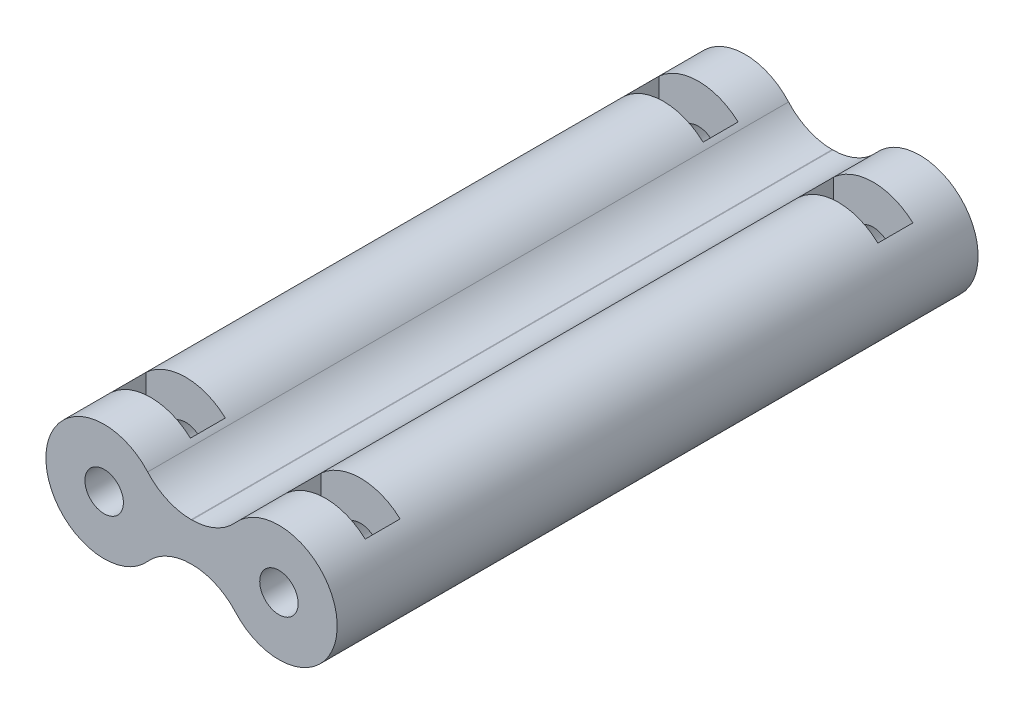
SolidWorks part; units mm, degrees
ref_plane "Plano frontal" through (0, 0, 0) normal (0, 0, 1) x (1, 0, 0)
ref_plane "Plano superior" through (0, 0, 0) normal (0, 1, 0) x (1, 0, 0)
ref_plane "Plano direito" through (0, 0, 0) normal (1, 0, 0) x (0, 0, -1)
sketch "Esboço1" plane through (0, 0, 0) normal (0, 0, 1) x (1, 0, 0)
  line L0 (0, 0) -> (0, 3.1709) construction
  line L1 (-2.7801, 1.65) -> (2.7801, 1.65)
  line L2 (-2.7801, -1.65) -> (2.7801, -1.65)
  circle A0 centre (-7.5, 0) radius 1.65
  circle A1 centre (7.5, 0) radius 1.65
  arc A2 (-2.7801, 1.65) -> (-2.7801, -1.65) centre (-7.5, 0) ccw
  arc A3 (2.7801, -1.65) -> (2.7801, 1.65) centre (7.5, 0) ccw
  dimension "D1" = 3.3
  dimension "D3" = 10
  dimension "D2" = 15
extrude "Ressalto-extrusão1" add sketch "Esboço1" along normal blind 55
fillet "Filete1" radius 5 4 edges at (-2.7801, -1.65, 27.5) (2.7801, -1.65, 27.5) (2.7801, 1.65, 27.5) (-2.7801, 1.65, 27.5)
sketch "Esboço2" plane through (0, 0, 0) normal (0, 1, 0) x (1, 0, 0)
  line L0 (-7.5, 0) -> (-7.5, -55) construction
  line L1 (-5.85, 0) -> (-9.15, 0) construction
  line L2 (-12.5, -55) -> (-3.7658, -55) construction
  line L3 (-3.7658, 0) -> (-12.5, 0) construction
  line L4 (-10.9, -4) -> (-4.1, -4)
  line L5 (-10.9, -4) -> (-10.9, -7)
  line L6 (-10.9, -7) -> (-4.1, -7)
  line L7 (-4.1, -4) -> (-4.1, -7)
  line L8 (-10.9, -4) -> (-4.1, -7) construction
  line L9 (-10.9, -7) -> (-4.1, -4) construction
  line L10 (0, 0) -> (0, -55) construction
  line L11 (0.0316, -55) -> (-0.0316, -55) construction
  line L12 (-12.5, -27.5) -> (12.5, -27.5) construction
  line L13 (-12.5, 0) -> (-12.5, -55) construction
  line L14 (12.5, -55) -> (12.5, 0) construction
  line L15 (10.9, -7) -> (4.1, -4) construction
  line L16 (10.9, -4) -> (4.1, -7) construction
  line L17 (4.1, -4) -> (4.1, -7)
  line L18 (10.9, -7) -> (4.1, -7)
  line L19 (10.9, -4) -> (10.9, -7)
  line L20 (10.9, -4) -> (4.1, -4)
  line L21 (10.9, -51) -> (4.1, -48) construction
  line L22 (10.9, -48) -> (4.1, -51) construction
  line L23 (-10.9, -48) -> (-4.1, -51) construction
  line L24 (-10.9, -51) -> (-4.1, -48) construction
  line L25 (10.9, -51) -> (4.1, -51)
  line L26 (10.9, -51) -> (10.9, -48)
  line L27 (10.9, -48) -> (4.1, -48)
  line L28 (4.1, -51) -> (4.1, -48)
  line L29 (-4.1, -51) -> (-4.1, -48)
  line L30 (-10.9, -48) -> (-4.1, -48)
  line L31 (-10.9, -51) -> (-10.9, -48)
  line L32 (-10.9, -51) -> (-4.1, -51)
  point P6 (-7.5, -5.5)
  point P28 (7.5, -5.5)
  point P37 (7.5, -49.5)
  point P38 (-7.5, -49.5)
  dimension "D1" = 3
  dimension "D2" = 6.8
  dimension "D3" = 4
extrude "Corte-extrusão1" cut sketch "Esboço2" against normal through all both and the other way through all contours L7 L4 L5 L6 | L19 L20 L17 L18 | L28 L25 L26 L27 | L31 L32 L29 L30 region at (-7.5, 0, 5.5) region at (7.5, 0, 5.5) region at (7.5, 0, 49.5) region at (-7.5, 0, 49.5)
